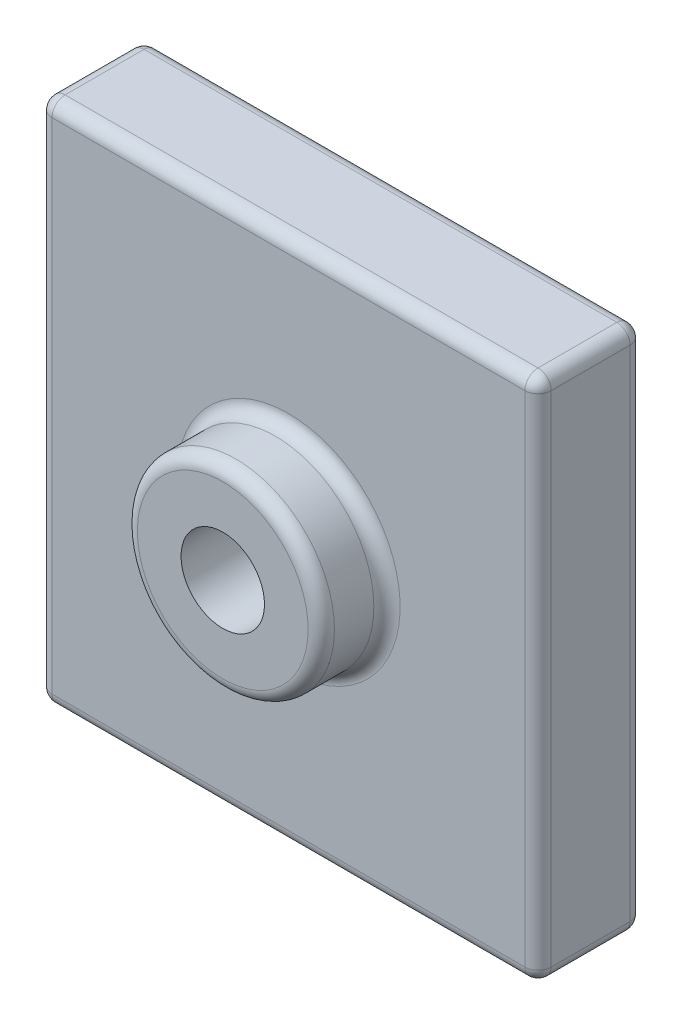
SolidWorks part; units mm, degrees
ref_plane "Front Plane" through (0, 0, 0) normal (0, 0, 1) x (1, 0, 0)
ref_plane "Top Plane" through (0, 0, 0) normal (0, 1, 0) x (1, 0, 0)
ref_plane "Right Plane" through (0, 0, 0) normal (1, 0, 0) x (0, 0, -1)
sketch "Sketch1" plane through (0, 0, 0) normal (0, 0, 1) x (1, 0, 0)
  line L1 (0, 0) -> (38, 0)
  line L2 (0, 0) -> (0, 40)
  line L3 (0, 40) -> (38, 40)
  line L4 (38, 0) -> (38, 40)
  dimension "D1" = 38
  dimension "D2" = 40
extrude "Boss-Extrude1" add sketch "Sketch1" along normal blind 8
sketch "Sketch2" plane through (0, 0, 8) normal (0, 0, 1) x (1, 0, 0)
  line L4 (0, 40) -> (0, 0)
  line L5 (0, 0) -> (38, 0)
  line L6 (38, 0) -> (38, 40)
  line L7 (38, 40) -> (0, 40)
  line L8 (0, 40) -> (0, 0) construction
  line L9 (0, 0) -> (38, 0) construction
  line L10 (38, 0) -> (38, 40) construction
  line L11 (38, 40) -> (0, 40) construction
  circle A0 centre (19, 20) radius 7.5
  circle A1 centre (19, 20) radius 3.175
  point P2 (19, 20)
  point P4 (0, 20)
  point P6 (19, 0)
  dimension "D2" = 15
  dimension "D3" = 6.35
  dimension "D1" = 0
extrude "Boss-Extrude2" add sketch "Sketch2" along normal blind 5
fillet "Fillet1" radius 1 14 edges at (26.5, 20, 13) (19, 0, 0) (19, 40, 0) (38, 0, 4) (38, 40, 4) (38, 20, 0) (0, 40, 4) (0, 0, 4) (0, 20, 0) (26.5, 20, 8) (19, 40, 8) (38, 20, 8) (19, 0, 8) (0, 20, 8)
sketch "Sketch3" plane through (0, 0, 0) normal (0, 0, -1) x (-1, 0, 0)
  line L4 (-1, 39) -> (-37, 39)
  line L5 (-37, 39) -> (-37, 1)
  line L6 (-37, 1) -> (-1, 1)
  line L7 (-1, 1) -> (-1, 39)
  line L8 (-1, 39) -> (-37, 39) construction
  line L9 (-37, 39) -> (-37, 1) construction
  line L10 (-37, 1) -> (-1, 1) construction
  line L11 (-1, 1) -> (-1, 39) construction
  line L15 (-15.7921, 25.5563) -> (-22.2079, 25.5563)
  line L16 (-22.2079, 25.5563) -> (-25.4158, 20)
  line L17 (-25.4158, 20) -> (-22.2079, 14.4438)
  line L18 (-22.2079, 14.4438) -> (-15.7921, 14.4438)
  line L19 (-15.7921, 14.4438) -> (-12.5842, 20)
  line L20 (-12.5842, 20) -> (-15.7921, 25.5563)
  circle A0 centre (-19, 20) radius 5.5562 construction
  point P2 (-19, 39)
  point P4 (-37, 20)
  point P6 (-19, 20)
  dimension "D2" = 11.1125
  dimension "D1" = 0
extrude "Cut-Extrude1" cut sketch "Sketch3" against normal blind 5.5562
sketch "Sketch4" plane through (0, 0, 0) normal (0, 0, -1) x (-1, 0, 0)
  circle A0 centre (-19, 20) radius 3.175 construction
  circle A1 centre (-19, 20) radius 3.175
extrude "Cut-Extrude2" cut sketch "Sketch4" against normal through all
